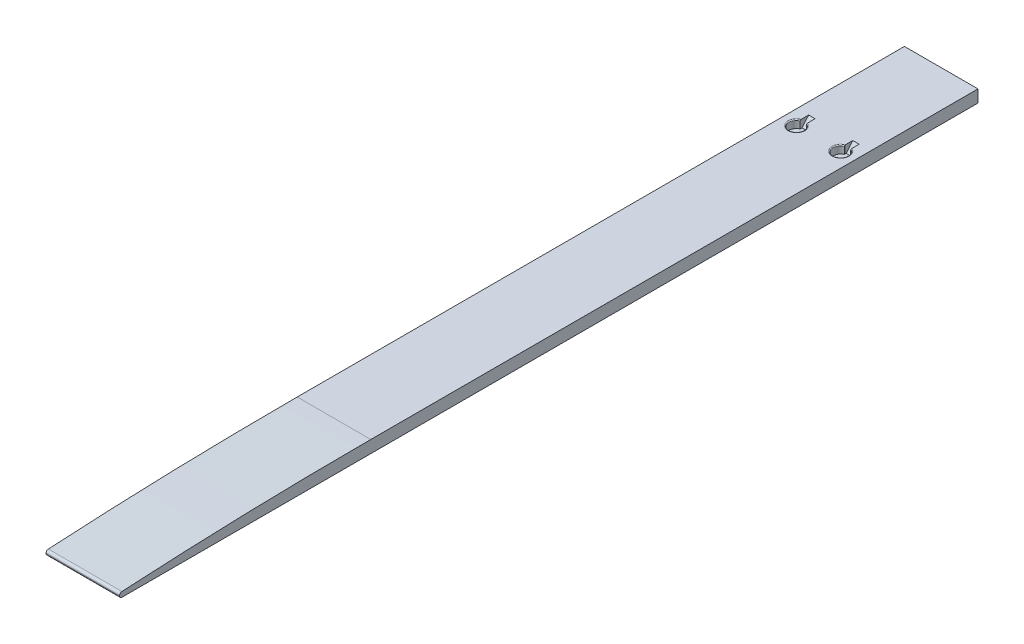
SolidWorks part; units mm, degrees
other "标注1"
sketch "草图6" plane through (0, 5, 350) normal (-0.6393, 0.5849, 0.4992) x (0.7619, 0.3939, 0.5141)
sketch "草图7" plane through (0, 5, 350) normal (-0.6393, 0.5849, 0.4992) x (0.7619, 0.3939, 0.5141)
sketch "草图8" plane through (0, 5, 350) normal (-0.6393, 0.5849, 0.4992) x (0.7619, 0.3939, 0.5141)
sketch "草图9" plane through (0, 5, 350) normal (-0.6393, 0.5849, 0.4992) x (0.7619, 0.3939, 0.5141)
ref_plane "前视基准面" through (0, 0, 0) normal (0, 0, 1) x (1, 0, 0)
ref_plane "上视基准面" through (0, 0, 0) normal (0, 1, 0) x (1, 0, 0)
ref_plane "右视基准面" through (0, 0, 0) normal (1, 0, 0) x (0, 0, -1)
other "Configuration Table"
sketch "草图1" plane through (0, 0, 0) normal (1, 0, 0) x (0, 0, -1)
  line L0 (0, 0) -> (-350, 0)
  line L5 (0, 5) -> (0, 0)
  line L6 (-300, 5) -> (0, 5)
  line L7 (-350, 0) -> (-350, 2)
  line L8 (-350, 2) -> (-300, 5)
  dimension "D1" = 350
  dimension "D2" = 5
  dimension "D3" = 2
  dimension "D7" = 50
extrude "凸台-拉伸1" add sketch "草图1" along normal blind 30
fillet "圆角1" radius 1750 1 edges at (15, 5, 300)
sketch "草图4" plane through (0, 5, 0) normal (0, 1, 0) x (1, 0, 0)
  line L0 (30, 0) -> (30, -247.5744) construction
  line L2 (15, 0) -> (15, -26.6679) construction
  line L3 (30, 0) -> (0, 0) construction
  line L4 (30, -350) -> (0, -350) construction
  circle A0 centre (24, -50) radius 3.1
  circle A1 centre (6, -50) radius 3.1
  dimension "D2" = 6.2
  dimension "D1" = 6
  dimension "D3" = 300
extrude "切除-拉伸3" cut sketch "草图4" against normal blind 3.2
fillet "圆角4" radius 0.4 2 edges at (24, 5, 53.1) (6, 5, 46.9)
sketch "草图5" plane through (0, 0, 0) normal (0, 0, -1) x (-1, 0, 0)
  line L0 (0, 0) -> (0, 5) construction
  line L1 (-25, 3.5) -> (-5, 3.5)
  line L2 (-25, 3.5) -> (-25, 1.5)
  line L3 (-25, 1.5) -> (-5, 1.5)
  line L4 (-5, 3.5) -> (-5, 1.5)
  line L5 (-30, 0) -> (-30, 5) construction
  line L6 (-30, 5) -> (0, 5) construction
  line L7 (-30, 0) -> (0, 0) construction
  dimension "D1" = 5
  dimension "D2" = 5
  dimension "D3" = 1.5
  dimension "D4" = 1.5
extrude "切除-拉伸4" cut sketch "草图5" against normal blind 25
fillet "圆角5" radius 1 2 edges at (15, 0, 350) (15, 2, 350)
fillet "圆角6" radius 1 2 edges at (15, 1.5, 0) (15, 3.5, 0)
sketch "草图10" plane through (0, 5, 0) normal (0, 1, 0) x (1, 0, 0)
  line L0 (15, 0) -> (15, -33.6975) construction
  line L1 (7.3025, -46.7514) -> (7.3062, -46.7514)
  line L2 (4.6975, -46.7514) -> (4.6975, -43.7514)
  line L3 (4.6975, -43.7514) -> (7.3062, -43.7514)
  line L4 (7.3062, -46.7514) -> (7.3062, -43.7514)
  line L5 (30, 0) -> (0, 0) construction
  line L6 (25.3025, -46.7514) -> (25.3025, -43.7514)
  line L7 (25.3025, -43.7514) -> (22.6938, -43.7514)
  line L8 (22.6938, -46.7514) -> (22.6938, -43.7514)
  line L9 (22.6975, -46.7514) -> (22.6938, -46.7514)
  line L10 (4.6975, -46.7514) -> (4.6975, -47.1869)
  line L11 (7.3025, -46.7514) -> (7.3025, -47.1869)
  line L12 (22.6975, -46.7514) -> (22.6975, -47.1869)
  line L13 (25.3025, -46.7514) -> (25.3025, -47.1869)
  circle A0 centre (6, -50) radius 3.5 construction
  circle A3 centre (6, -50) radius 3.1 construction
  arc A4 (7.3025, -47.1869) -> (4.6975, -47.1869) centre (6, -50) ccw
  circle A5 centre (24, -50) radius 3.1 construction
  arc A6 (25.3025, -47.1869) -> (22.6975, -47.1869) centre (24, -50) ccw
  dimension "D1" = 2.6088
  dimension "D2" = 3
extrude "切除-拉伸5" cut sketch "草图10" against normal up to surface (3.2 mm away) up to face at (6, 1.8, 46.9)
chamfer "倒角1" distance 3.2 angle 40 2 edges at (23.9981, 1.8, 43.7514) (6.0019, 1.8, 43.7514) first distance on face at (23.9981, 3.4, 43.7514) first distance on face at (6.0019, 3.4, 43.7514)
